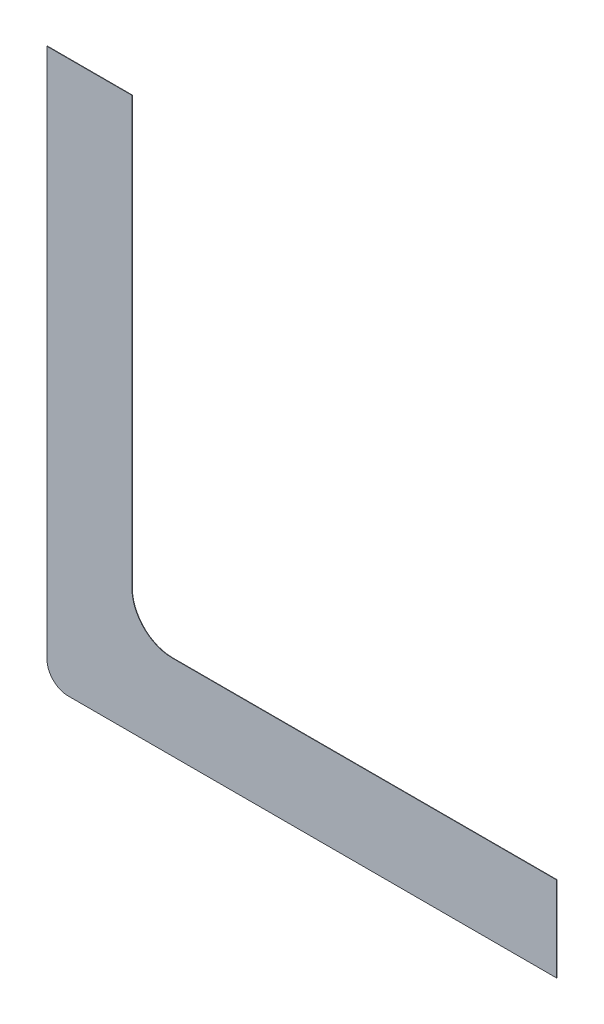
SolidWorks part; units mm, degrees
ref_plane "前视基准面" through (0, 0, 0) normal (0, 0, 1) x (1, 0, 0)
ref_plane "上视基准面" through (0, 0, 0) normal (0, 1, 0) x (1, 0, 0)
ref_plane "右视基准面" through (0, 0, 0) normal (1, 0, 0) x (0, 0, -1)
sketch "草图1" plane through (0, 0, 0) normal (0, 0, 1) x (1, 0, 0)
  line L0 (0, 0) -> (-120, 0)
  line L1 (-120, 0) -> (-120, 130)
  line L2 (-120, 130) -> (-100, 130)
  line L3 (-100, 130) -> (-100, 20)
  line L4 (-100, 20) -> (0, 20)
  line L5 (0, 20) -> (0, 0)
  dimension "D1" = 130
  dimension "D2" = 120
  dimension "D3" = 20
  dimension "D4" = 20
extrude "凸台-拉伸1" add sketch "草图1" along normal blind 0.1
fillet "圆角1" radius 9.5 1 edges at (-100, 20, 0.05)
fillet "圆角2" radius 5 1 edges at (-120, 0, 0.05)
sketch3d "3D草图2"
  line L0 (-100, 29.5, 0.1) -> (-100, 130, 0.1) construction
  line L1 (0, 20, 0.1) -> (-90.5, 20, 0.1) construction
  point P0 (-100, 117, 0.1)
  point P1 (-100, 78.9323, 0.1)
  point P4 (-80, 20, 0.1)
  point P5 (-15, 20, 0.1)
  point P8 (0, 0, 0)
  point P9 (0, 0, 0)
  point P10 (0, 0, 0)
  point P11 (0, 0, 0)
  point P12 (0, 0, 0)
  point P13 (0, 0, 0)
sketch3d "3D草图1" [suppressed]
  line L0 (-11.5, 30, 0.5) -> (-11.5, 100, 0.5) construction
  arc A0 (-1.5, 20, 0.5) -> (-11.5, 30, 0.5) centre (-1.5, 30, 0.5) ccw construction
  point P0 (-1.5, 20, 0.5)
  point P1 (-8.5711, 22.9289, 0.5)
  point P3 (-11.5, 30, 0.5)
  point P7 (-1.5, 30, -9.5)
  point P8 (-11.5, 49.1552, 0.5)
  point P10 (-11.5, 87.2694, 0.5)
